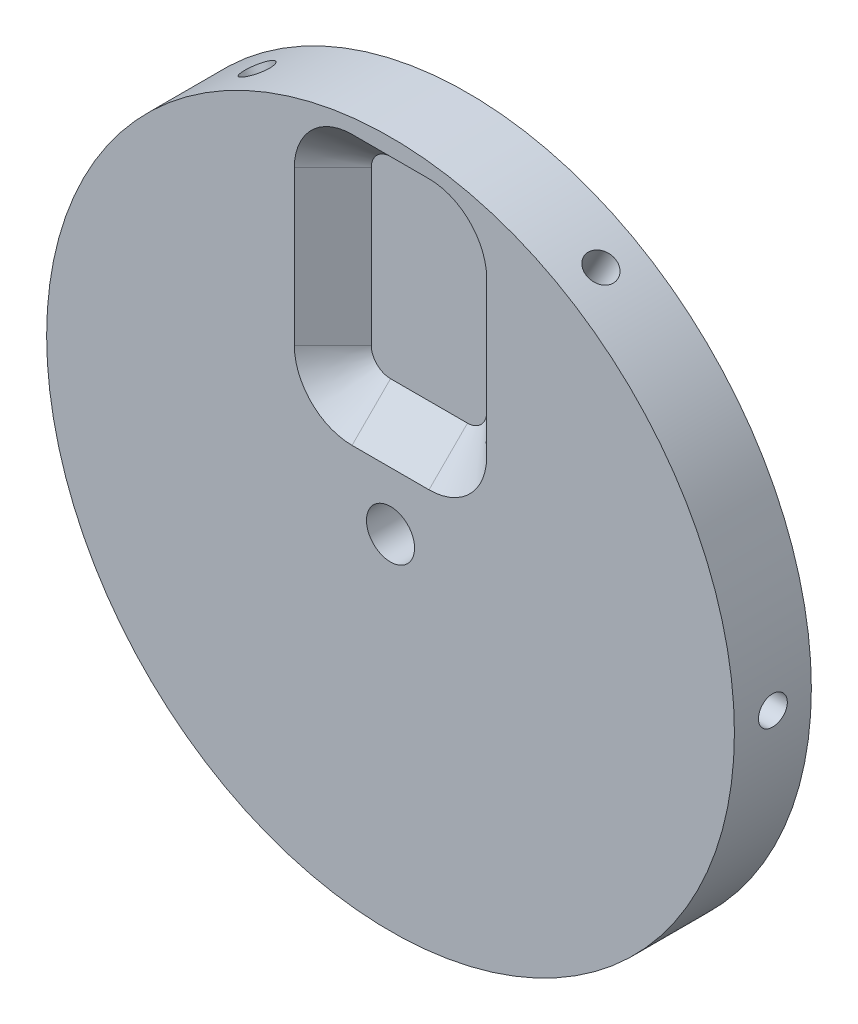
SolidWorks part; units mm, degrees
material "ABS"
ref_plane "Front Plane" through (0, 0, 0) normal (0, 0, 1) x (1, 0, 0)
ref_plane "Top Plane" through (0, 0, 0) normal (0, 1, 0) x (1, 0, 0)
ref_plane "Right Plane" through (0, 0, 0) normal (1, 0, 0) x (0, 0, -1)
sketch "Sketch1" plane through (0, 0, 0) normal (0, 0, 1) x (1, 0, 0)
  circle A0 centre (0, 0) radius 45.4025
  dimension "D1" = 90.805
extrude "Boss-Extrude1" add sketch "Sketch1" along normal blind 10.16
sketch "Sketch2" plane through (0, 0, 0) normal (1, 0, 0) x (0, 0, -1)
  line L0 (-10.16, 0) -> (0, 0) construction
  line L1 (-10.16, 45.4025) -> (-10.16, -45.4025) construction
  circle A0 centre (-5.08, 0) radius 1.905
  point P2 (-7.62, 0)
  point P6 (-5.08, 0)
  dimension "D1" = 3.81
extrude "Cut-Extrude1" cut sketch "Sketch2" along normal blind 7.62 from offset 38.1
ref_axis "Axis1" through (0, 0, 10.16) along (0, 0, -1)
pattern_circular "CirPattern1" count 6 every 60 about axis through (0, 0, 10.16) along (0, 0, -1) of "Cut-Extrude1"
sketch "Sketch3" plane through (0, 0, 0) normal (0, 0, -1) x (-1, 0, 0)
  circle A0 centre (0, 0) radius 3.175
  dimension "D1" = 6.35
extrude "Cut-Extrude2" cut sketch "Sketch3" against normal through all
sketch "Sketch4" plane through (0, 0, 10.16) normal (0, 0, 1) x (1, 0, 0)
  line L1 (-5.08, 38.1) -> (5.08, 38.1)
  line L2 (-7.62, 35.56) -> (-7.62, 15.24)
  line L3 (-5.08, 12.7) -> (5.08, 12.7)
  line L4 (7.62, 35.56) -> (7.62, 15.24)
  arc A0 (-7.62, 15.24) -> (-5.08, 12.7) centre (-5.08, 15.24) ccw
  arc A1 (5.08, 12.7) -> (7.62, 15.24) centre (5.08, 15.24) ccw
  arc A2 (5.08, 38.1) -> (7.62, 35.56) centre (5.08, 35.56) cw
  arc A3 (-5.08, 38.1) -> (-7.62, 35.56) centre (-5.08, 35.56) ccw
  point P4 (8.2658, 9.161)
  point P6 (0, 12.7)
  point P9 (-7.62, 12.7)
  point P12 (7.62, 12.7)
  point P17 (-7.62, 38.1)
  dimension "D4" = 2.54
  dimension "D1" = 12.7
  dimension "D2" = 25.4
  dimension "D3" = 15.24
extrude "Cut-Extrude3" cut sketch "Sketch4" against normal blind 5.08
chamfer "Chamfer2" distance 5.08 angle 45 8 edges at (0, 12.7, 10.16) (6.8761, 13.4439, 10.16) (-6.8761, 13.4439, 10.16) (7.62, 25.4, 10.16) (-7.62, 25.4, 10.16) (6.8761, 37.3561, 10.16) (-6.8761, 37.3561, 10.16) (0, 38.1, 10.16)
